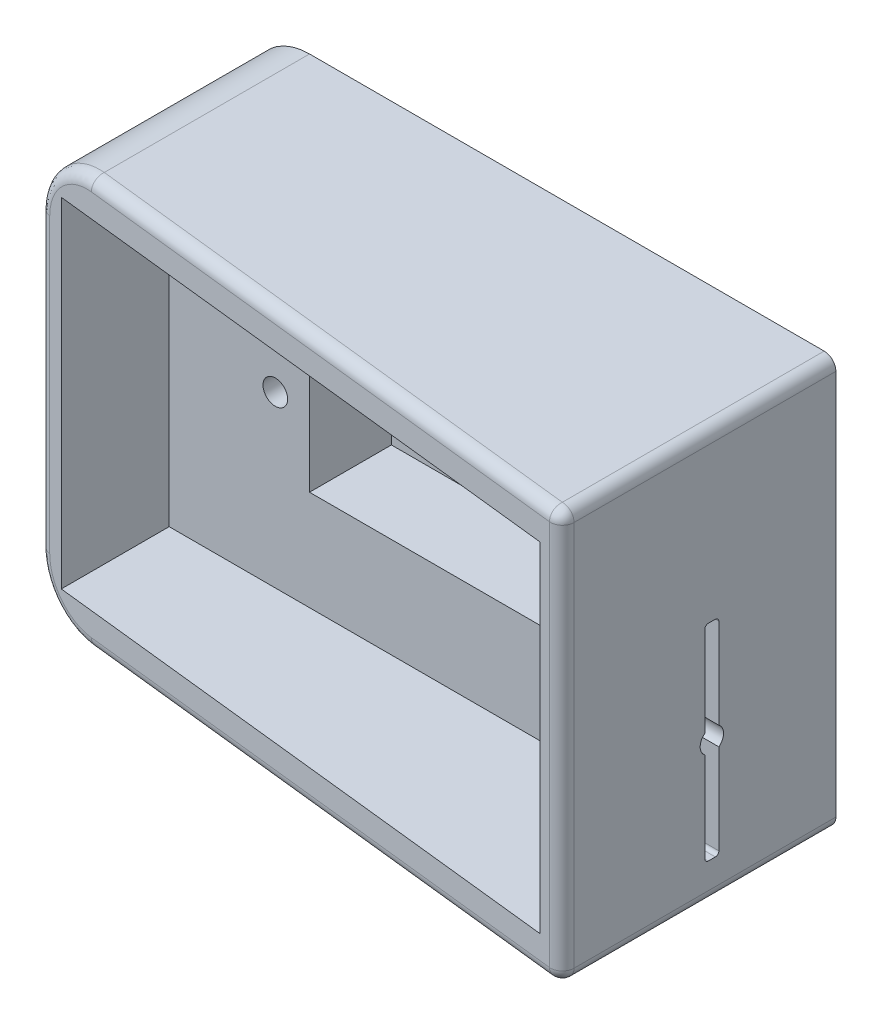
SolidWorks part; units mm, degrees
material "ABS"
ref_plane "Front Plane" through (0, 0, 0) normal (0, 0, 1) x (1, 0, 0)
ref_plane "Top Plane" through (0, 0, 0) normal (0, 1, 0) x (1, 0, 0)
ref_plane "Right Plane" through (0, 0, 0) normal (1, 0, 0) x (0, 0, -1)
sketch "Sketch1" plane through (0, 0, 0) normal (0, 0, 1) x (1, 0, 0)
  line L1 (-25, 17.5) -> (25, 17.5)
  line L2 (-25, 17.5) -> (-25, -17.5)
  line L3 (-25, -17.5) -> (25, -17.5)
  line L4 (25, 17.5) -> (25, -17.5)
  line L5 (-25, 17.5) -> (25, -17.5) construction
  line L6 (-25, -17.5) -> (25, 17.5) construction
  point P0 (0, 0)
  dimension "D1" = 50
  dimension "D2" = 35
extrude "Boss-Extrude1" add sketch "Sketch1" along normal blind 24
sketch "Sketch2" plane through (0, 0, 24) normal (0, 0, 1) x (1, 0, 0)
  line L0 (25, 17.5) -> (-25, 17.5) construction
  line L1 (-23, 14.5) -> (23, 14.5)
  line L2 (-23, 14.5) -> (-23, -14.5)
  line L3 (-23, -14.5) -> (23, -14.5)
  line L4 (23, 14.5) -> (23, -14.5)
  line L5 (-23, 14.5) -> (23, -14.5) construction
  line L6 (-23, -14.5) -> (23, 14.5) construction
  line L8 (25, -17.5) -> (25, 17.5) construction
  point P0 (0, 0)
  dimension "D1" = 3
  dimension "D2" = 2
extrude "Cut-Extrude1" cut sketch "Sketch2" against normal blind 15
sketch "Sketch3" plane through (-25, 0, 0) normal (-1, 0, 0) x (0, 0, 1)
  line L5 (24, -17.5) -> (0, -17.5) construction
  line L6 (24, 17.5) -> (18.003, 17.5)
  line L7 (24, 17.5) -> (24, -17.5)
  line L8 (24, -17.5) -> (18.003, -17.5)
  line L9 (18.003, 17.5) -> (18.003, -17.5)
  dimension "D1" = 5.997
sketch "Sketch5" plane through (25, 0, 0) normal (1, 0, 0) x (0, 0, -1)
  line L0 (-24, -17.5) -> (-18.003, -17.5) construction
  line L1 (-24, 17.5) -> (-23.5, 17.5)
  line L2 (-24, 17.5) -> (-24, -17.5)
  line L3 (-24, -17.5) -> (-23.5, -17.5)
  line L4 (-23.5, 17.5) -> (-23.5, -17.5)
  dimension "D1" = 0.5
loft "Cut-Loft4" cut profiles "Sketch3", "Sketch5" connector at (-25, 17.5, 18.003) connector at (25, 17.5, 23.5)
sketch "Sketch8" plane through (0, 0, 9) normal (0, 0, 1) x (1, 0, 0)
  line L1 (11, -5.95) -> (-11, -5.95)
  line L2 (11, -5.95) -> (11, 5.95)
  line L3 (11, 5.95) -> (-11, 5.95)
  line L4 (-11, -5.95) -> (-11, 5.95)
  line L5 (11, -5.95) -> (-11, 5.95) construction
  line L6 (11, 5.95) -> (-11, -5.95) construction
  point P0 (0, 0)
  dimension "D1" = 22
  dimension "D2" = 11.9
extrude "Cut-Extrude2" cut sketch "Sketch8" against normal blind 7
sketch "Sketch9" plane through (0, 0, 9) normal (0, 0, 1) x (1, 0, 0)
  line L0 (0, 9.5638) -> (0, -11.7065) construction
  line L1 (-11, 5.95) -> (-11, -5.95) construction
  circle A0 centre (-13.925, 0) radius 1.05
  circle A1 centre (13.925, 0) radius 1.05
  dimension "D1" = 2.1
  dimension "D2" = 2.925
extrude "Cut-Extrude3" cut sketch "Sketch9" against normal blind 6
sketch "Sketch11" plane through (0, 0, 2) normal (0, 0, 1) x (1, 0, 0)
  line L0 (-11, 5.95) -> (-11, -5.95) construction
  circle A0 centre (-5.25, 0) radius 3.5
  dimension "D2" = 7
  dimension "D1" = 5.75
extrude "Cut-Extrude5" cut sketch "Sketch11" against normal through all
fillet "Fillet5" radius 5 2 edges
fillet "Fillet6" radius 1 5 edges at (-23.5355, -16.0355, 18.164) (-23.5355, 16.0355, 18.164)
fillet "Fillet7" radius 1 5 edges at (25, -17.2071, 23.2053) (25, 17.2071, 23.2053)
sketch "Sketch13" plane through (23, 0, 0) normal (-1, 0, 0) x (0, 0, 1)
  line L3 (23.2801, 14.5) -> (23.2801, -14.5) construction
  line L4 (8.9422, -5.5) -> (13.1986, -5.5) construction
  line L10 (10.9031, -14.3) -> (10.3031, -14.3)
  line L12 (11.2031, -14) -> (11.2031, -6.3)
  line L17 (10.0031, -14) -> (10.0031, -6.3)
  line L18 (11.2031, -14.3) -> (10.0031, -6.3) construction
  line L19 (11.2031, -6.3) -> (10.0031, -14.3) construction
  line L20 (10.9031, 3.3) -> (10.3031, 3.3)
  line L21 (10.0031, 3) -> (10.0031, -4.7)
  line L22 (11.2031, 3) -> (11.2031, -4.7)
  line L23 (0, -17.5) -> (22.384, -17.5) construction
  arc A5 (10.0031, -4.7) -> (10.0031, -6.3) centre (10.6031, -5.5) ccw
  arc A6 (10.3031, -14.3) -> (10.0031, -14) centre (10.3031, -14) cw
  arc A7 (10.9031, -14.3) -> (11.2031, -14) centre (10.9031, -14) ccw
  arc A8 (10.3031, 3.3) -> (10.0031, 3) centre (10.3031, 3) ccw
  arc A9 (10.9031, 3.3) -> (11.2031, 3) centre (10.9031, 3) cw
  arc A10 (11.2031, -6.3) -> (11.2031, -4.7) centre (10.6031, -5.5) ccw
  point P6 (10.6031, -10.3)
  dimension "D5" = 2
  dimension "D6" = 0.3
  dimension "D1" = 12
  dimension "D2" = 12.677
  dimension "D3" = 1.2
  dimension "D4" = 8
sketch "Sketch14" plane through (0, 0, 9) normal (0, 0, 1) x (1, 0, 0)
  line L0 (23, -14.5) -> (23, 14.5) construction
  line L1 (23, 9.8365) -> (18.435, 9.8365)
  line L2 (23, 9.8365) -> (23, -14.5)
  line L3 (23, -14.5) -> (18.435, -14.5)
  line L4 (18.435, 9.8365) -> (18.435, -14.5)
  line L5 (-23, -14.5) -> (23, -14.5) construction
extrude "Cut-Extrude6" cut sketch "Sketch14" against normal blind 4
extrude "Cut-Extrude7" cut sketch "Sketch13" against normal through all
